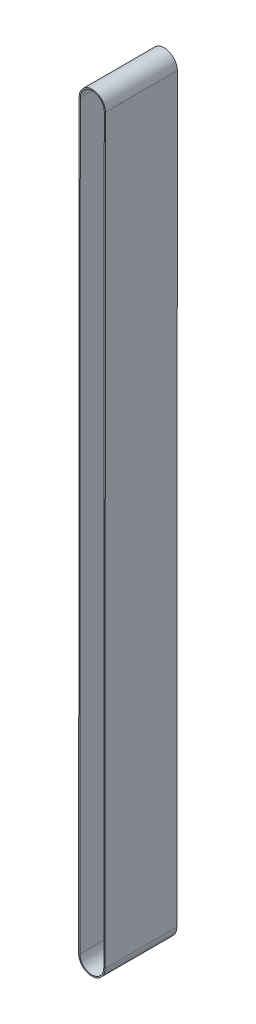
SolidWorks part; units mm, degrees
ref_plane "Front Plane" through (0, 0, 0) normal (0, 0, 1) x (1, 0, 0)
ref_plane "Top Plane" through (0, 0, 0) normal (0, 1, 0) x (1, 0, 0)
ref_plane "Right Plane" through (0, 0, 0) normal (1, 0, 0) x (0, 0, -1)
sketch "Sketch1" plane through (0, 0, 0) normal (0, 0, 1) x (1, 0, 0)
  line L0 (-96, 3110.0156) -> (-100, -3080)
  line L1 (100, -3080) -> (104, 3110.0156)
  circle A0 centre (4, 3110.0156) radius 100 construction
  arc A1 (103.9999, 3109.8864) -> (-96, 3110.0156) centre (4, 3110.0156) ccw
  arc A3 (-99.9999, -3079.8708) -> (100, -3080) centre (0, -3080) ccw
  point P4 (0, 0)
  point P5 (0, 0)
  point P11 (0, 0)
extrude "Extrude-Thin3" add sketch "Sketch1" along normal mid plane 600 thin thin type one direction wall 10
